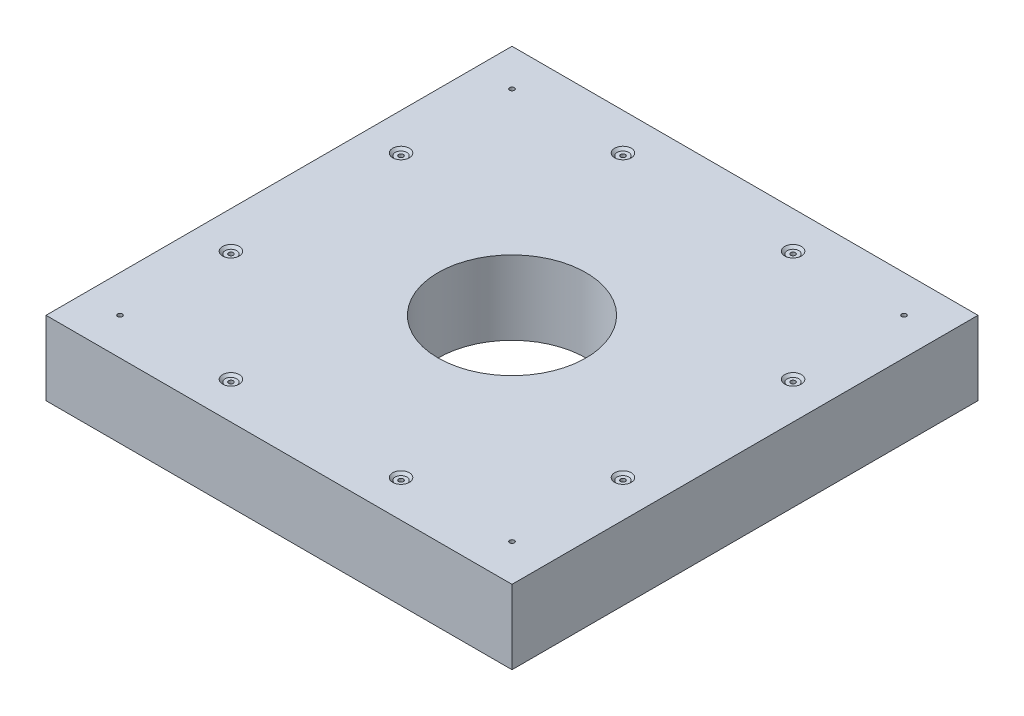
SolidWorks part; units mm, degrees
ref_plane "Front Plane" through (0, 0, 0) normal (0, 0, 1) x (1, 0, 0)
ref_plane "Top Plane" through (0, 0, 0) normal (0, 1, 0) x (1, 0, 0)
ref_plane "Right Plane" through (0, 0, 0) normal (1, 0, 0) x (0, 0, -1)
sketch "Sketch1" plane through (0, 0, 0) normal (0, 1, 0) x (1, 0, 0)
  line L5 (-80, -80) -> (80, -80)
  line L6 (-80, -80) -> (-80, 80)
  line L7 (-80, 80) -> (80, 80)
  line L8 (80, -80) -> (80, 80)
  line L9 (-80, -80) -> (80, 80) construction
  line L10 (-80, 80) -> (80, -80) construction
  point P0 (0, 0)
  dimension "D1" = 160
  dimension "D2" = 160
extrude "Boss-Extrude1" add sketch "Sketch1" along normal blind 25.4
hole_wizard "CBORE for #0 Binding Head Machine Screw1" positions "Sketch2" profile "Sketch3" counterbore size "#0" standard "ANSI Inch" end condition through all
sketch "Sketch2" plane through (0, 0, 0) normal (0, 1, 0) x (1, 0, 0)
  line L0 (-80, -80) -> (80, -80) construction
  line L1 (-80, 80) -> (-80, -80) construction
  line L2 (0, 0) -> (112.6922, 0) construction
  line L5 (0, 0) -> (0, 110.9847) construction
  point P0 (-67.3, 67.3)
  point P2 (67.3, 67.3)
  point P4 (67.3, -67.3)
  point P6 (-67.3, -67.3)
  dimension "D1" = 12.7
  dimension "D2" = 12.7
sketch "Sketch3" plane through (-67.3, 0, -67.3) normal (1, 0, 0) x (0, 0, -1)
  line L0 (0, 0) -> (0, 25.4)
  line L1 (0, 25.4) -> (0.8065, 25.4)
  line L3 (0.8065, 25.4) -> (0.8065, 0.8128)
  line L4 (1.985, 0.8128) -> (0.8065, 0.8128)
  line L5 (1.985, 0.8128) -> (1.985, 0.8725)
  line L6 (1.985, 0.8725) -> (2.8575, 0)
  line L7 (2.8575, 0) -> (0, 0)
  line L8 (-1.985, 0.8725) -> (-2.8575, 0) construction
  line L11 (0, -6.35) -> (0, 107.95) construction
  dimension "Thru Hole Dia." = 1.6129
  dimension "Thru Hole Depth" = 25.4
  dimension "C'Bore Dia." = 3.97
  dimension "C'Bore Depth" = 0.8128
  dimension "Near C'Sink Dia." = 5.715
  dimension "Near C'Sink Angle" = 90
ref_axis "Axis1" through (0, 26.67, 0) along (0, -1, 0)
hole_wizard "CBORE for #0 Binding Head Machine Screw2" positions "Sketch4" profile "Sketch5" counterbore size "#0" standard "ANSI Inch" end condition through all
sketch "Sketch4" plane through (0, 25.4, 0) normal (0, 1, 0) x (1, 0, 0)
  line L1 (-80, 80) -> (-80, -80) construction
  circle A0 centre (-67.3, 67.3) radius 0.8065 construction
  circle A1 centre (-67.3, -67.3) radius 0.8065 construction
  point P0 (-67.3005, 29.2)
  point P2 (-67.3005, -29.2)
  dimension "D1" = 38.1
  dimension "D2" = 38.1
  dimension "D3" = 12.6995
sketch "Sketch5" plane through (-67.3005, 25.4, -29.2) normal (1, 0, 0) x (0, 0, 1)
  line L0 (0, 0) -> (0, 25.4)
  line L1 (0, 25.4) -> (0.8065, 25.4)
  line L3 (0.8065, 25.4) -> (0.8065, 0.8128)
  line L4 (1.985, 0.8128) -> (0.8065, 0.8128)
  line L5 (1.985, 0.8128) -> (1.985, 0.8725)
  line L6 (1.985, 0.8725) -> (2.8575, 0)
  line L7 (2.8575, 0) -> (0, 0)
  line L8 (-1.985, 0.8725) -> (-2.8575, 0) construction
  line L11 (0, -6.35) -> (0, 107.95) construction
  dimension "Thru Hole Dia." = 1.6129
  dimension "Thru Hole Depth" = 25.4
  dimension "C'Bore Dia." = 3.97
  dimension "C'Bore Depth" = 0.8128
  dimension "Near C'Sink Dia." = 5.715
  dimension "Near C'Sink Angle" = 90
pattern_circular "CirPattern1" count 4 over 360 about axis through (0, 26.67, 0) along (0, -1, 0) of "CBORE for #0 Binding Head Machine Screw2"
sketch "Sketch6" plane through (0, 25.4, 0) normal (0, 1, 0) x (1, 0, 0)
  circle A0 centre (0, 0) radius 25.4
extrude "Cut-Extrude1" cut sketch "Sketch6" against normal through all
